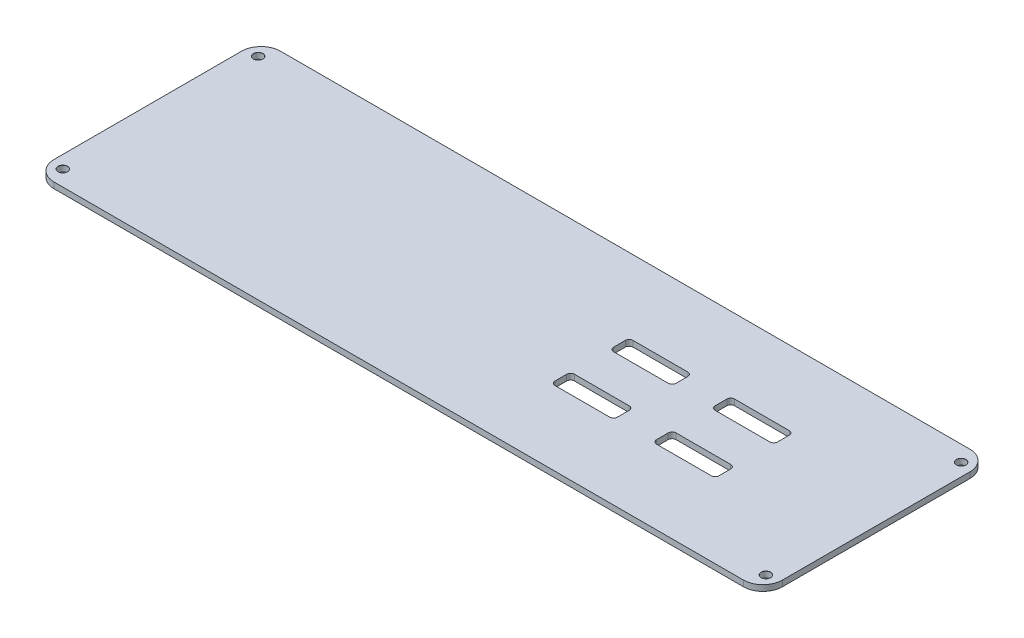
SolidWorks part; units mm, degrees
ref_plane "Front Plane" through (0, 0, 0) normal (0, 0, 1) x (1, 0, 0)
ref_plane "Top Plane" through (0, 0, 0) normal (0, 1, 0) x (1, 0, 0)
ref_plane "Right Plane" through (0, 0, 0) normal (1, 0, 0) x (0, 0, -1)
sketch "Sketch1" plane through (0, 0, 0) normal (0, 1, 0) x (1, 0, 0)
  line L1 (93.25, -29) -> (-93.25, -29)
  line L2 (93.25, -29) -> (93.25, 29)
  line L3 (93.25, 29) -> (-93.25, 29)
  line L4 (-93.25, -29) -> (-93.25, 29)
  line L5 (93.25, -29) -> (-93.25, 29) construction
  line L6 (93.25, 29) -> (-93.25, -29) construction
  point P0 (0, 0)
  dimension "D1" = 58
  dimension "D2" = 186.5
extrude "Boss-Extrude1" add sketch "Sketch1" along normal blind 1.5
fillet "Fillet1" radius 5 4 edges at (-93.25, 0.75, -29) (93.25, 0.75, -29) (93.25, 0.75, 29) (-93.25, 0.75, 29)
hole_wizard "M2 Clearance Hole1" positions "Sketch2" profile "Sketch3" hole size "M2" standard "ANSI Metric" end condition up to next
sketch "Sketch2" plane through (0, 1.5, 0) normal (0, 1, 0) x (1, 0, 0)
  line L0 (-90, -25) -> (-90, 25) construction
  line L1 (-90, 25) -> (90, 25) construction
  line L2 (90, 25) -> (-90, -25) construction
  line L6 (90, 25) -> (90, -25) construction
  line L7 (90, -25) -> (-90, -25) construction
  point P0 (-90, 25)
  point P2 (90, 25)
  point P4 (90, -25)
  point P6 (-90, -25)
  point P16 (0, 0)
  dimension "D1" = 180
  dimension "D2" = 50
sketch "Sketch3" plane through (-90, 1.5, -25) normal (1, 0, 0) x (0, 0, 1)
  line L0 (0, 0) -> (0, 1.5)
  line L1 (0, 1.5) -> (1.2, 1.5)
  line L2 (1.2, 1.5) -> (1.2, 0.025)
  line L3 (1.2, 0.025) -> (1.225, 0)
  line L5 (1.225, 0) -> (0, 0)
  line L6 (-1.2, 0.025) -> (-1.225, 0) construction
  line L11 (0, -6.35) -> (0, 107.95) construction
  dimension "Thru Hole Dia." = 2.4
  dimension "Thru Hole Depth" = 1.5
  dimension "Near C'Sink Dia." = 2.45
  dimension "Near C'Sink Angle" = 90
sketch "Sketch4" plane through (0, 1.5, 0) normal (0, 1, 0) x (1, 0, 0)
  line L0 (20, 5) -> (20, -5) construction
  line L1 (20, 10) -> (36, 10)
  line L2 (20, 10) -> (20, 5)
  line L3 (20, 5) -> (36, 5)
  line L4 (36, 10) -> (36, 5)
  line L5 (46, 10) -> (62, 10)
  line L6 (46, 10) -> (46, 5)
  line L7 (46, 5) -> (62, 5)
  line L8 (62, 10) -> (62, 5)
  line L9 (20, -5) -> (36, -5)
  line L10 (20, -5) -> (20, -10)
  line L11 (20, -10) -> (36, -10)
  line L12 (36, -5) -> (36, -10)
  line L13 (46, -5) -> (62, -5)
  line L14 (46, -5) -> (46, -10)
  line L15 (46, -10) -> (62, -10)
  line L16 (62, -5) -> (62, -10)
  line L17 (20, 0) -> (0, 0) construction
  point P19 (0, 0)
  point P20 (48.6113, -1.5587)
  point P21 (48.5942, -10.1014)
  point P22 (20.2143, 10)
  point P23 (46, 7.5)
  dimension "D1" = 16
  dimension "D2" = 5
  dimension "D3" = 10
  dimension "D4" = 20
  dimension "D5" = 10
extrude "Cut-Extrude1" cut sketch "Sketch4" against normal through all
fillet "Fillet2" radius 1 16 edges at (36, 0.75, -5) (20, 0.75, -5) (20, 0.75, -10) (62, 0.75, 5) (62, 0.75, 10) (46, 0.75, 10) (46, 0.75, 5) (36, 0.75, 5) (36, 0.75, 10) (20, 0.75, 10) (20, 0.75, 5) (62, 0.75, -10) (62, 0.75, -5) (46, 0.75, -5) (46, 0.75, -10) (36, 0.75, -10)
